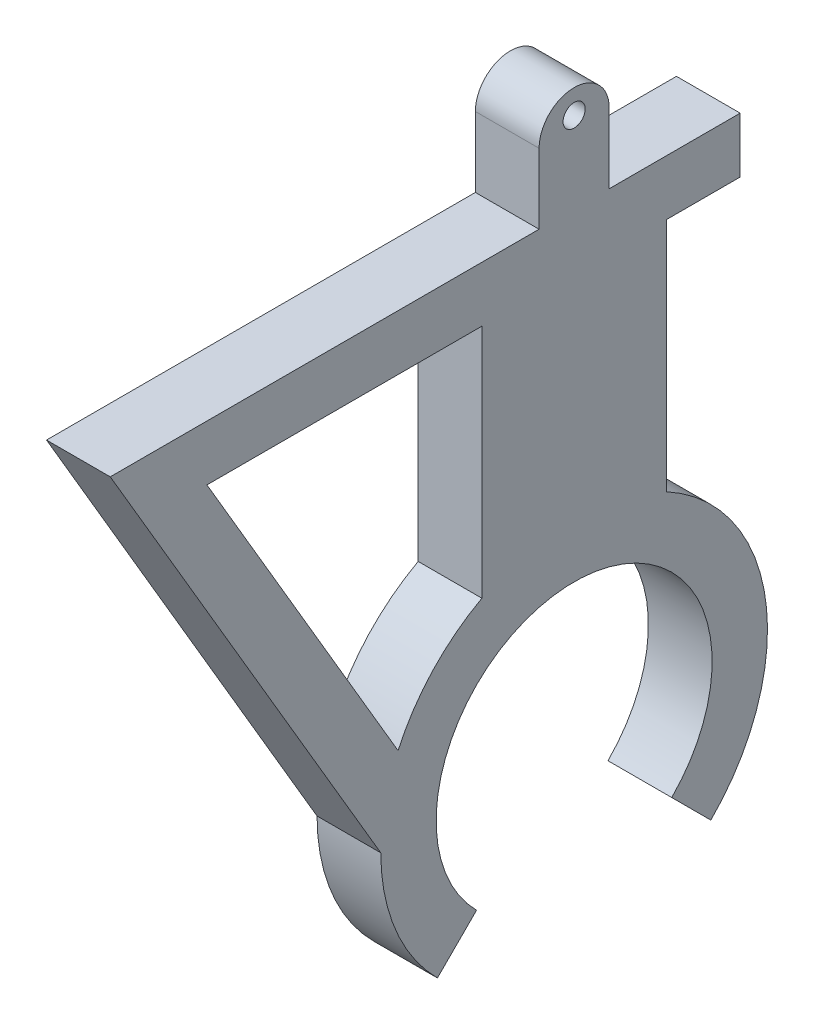
SolidWorks part; units mm, degrees
ref_plane "Front Plane" through (0, 0, 0) normal (0, 0, 1) x (1, 0, 0)
ref_plane "Top Plane" through (0, 0, 0) normal (0, 1, 0) x (1, 0, 0)
ref_plane "Right Plane" through (0, 0, 0) normal (1, 0, 0) x (0, 0, -1)
sketch "Sketch1" plane through (0, 0, 0) normal (1, 0, 0) x (0, 0, -1)
  line L0 (-2.6446, -2.6446) -> (2.6446, -2.6446) construction
  line L1 (-2.6446, -2.6446) -> (-3.7052, -3.7052)
  line L2 (3.7052, -3.7052) -> (2.6446, -2.6446)
  line L3 (0, 0) -> (0, 6.3411) construction
  line L4 (-2.5, 12.4907) -> (-0.95, 12.4907)
  line L5 (-2.5, 12.4907) -> (-2.5, 4.6052)
  line L6 (-0.95, 14.3907) -> (-0.95, 12.4907)
  line L7 (2.5, 12.4907) -> (2.5, 4.6052)
  line L8 (-2.5, 12.4907) -> (2.5, 4.6052) construction
  line L9 (-2.5, 4.6052) -> (2.5, 12.4907) construction
  line L10 (-0.95, 14.3907) -> (0.95, 14.3907) construction
  line L11 (0.95, 12.4907) -> (2.5, 12.4907)
  line L12 (0.95, 14.3907) -> (0.95, 12.4907)
  line L13 (-0.95, 14.3907) -> (0.95, 12.4907) construction
  line L14 (-0.95, 12.4907) -> (0.95, 14.3907) construction
  line L15 (-2.5, 12.4907) -> (-12.5716, 12.4907)
  line L16 (-12.5716, 12.4907) -> (-5.24, 0)
  line L17 (-2.5, 10.9907) -> (-9.9519, 10.9907)
  line L18 (-9.9519, 10.9907) -> (-4.7717, 2.1653)
  line L19 (-9.9519, 10.9907) -> (-3.9464, 0.7593) construction
  line L20 (-52.6576, 12.4907) -> (-57.4836, 12.4907) construction
  line L21 (2.5, 12.4907) -> (4.5, 12.4907)
  line L22 (2.5, 12.4907) -> (2.5, 10.9907)
  line L23 (2.5, 10.9907) -> (4.5, 10.9907)
  line L24 (4.5, 12.4907) -> (4.5, 10.9907)
  arc A0 (-2.6446, -2.6446) -> (2.6446, -2.6446) centre (0, 0) cw
  arc A1 (-3.7052, -3.7052) -> (-2.5, 4.6052) centre (0, 0) cw
  arc A2 (2.5, 4.6052) -> (3.7052, -3.7052) centre (0, 0) cw
  arc A3 (-3.7052, -3.7052) -> (3.7052, -3.7052) centre (0, 0) cw construction
  arc A4 (-0.95, 14.3907) -> (0.95, 14.3907) centre (0, 14.3907) cw
  circle A5 centre (0, 14.6907) radius 0.3
  point P7 (0, 8.5479)
  point P12 (0, 3.74)
  point P16 (0, 14.3907)
  point P17 (0, 13.4407)
  dimension "D1" = 3.74
  dimension "D3" = 1.5
  dimension "D6" = 1.9
  dimension "D8" = 0.6
  dimension "D9" = 1.5
  dimension "D2" = 90
  dimension "D5" = 5
  dimension "D7" = 1.9
  dimension "D10" = 2
extrude "Boss-Extrude1" add sketch "Sketch1" along normal blind 1.7272 contours A4 L6 L4 L5 A1 L1 A0 L2 A2 L7 L11 L12 A5 | L16 A1 L18 L17 L5 L15 | L24 L21 L7 L23 region at (0, 5.8984, 0) region at (0, 6.3266, 8.7674) region at (0, 11.7407, -3.5)
